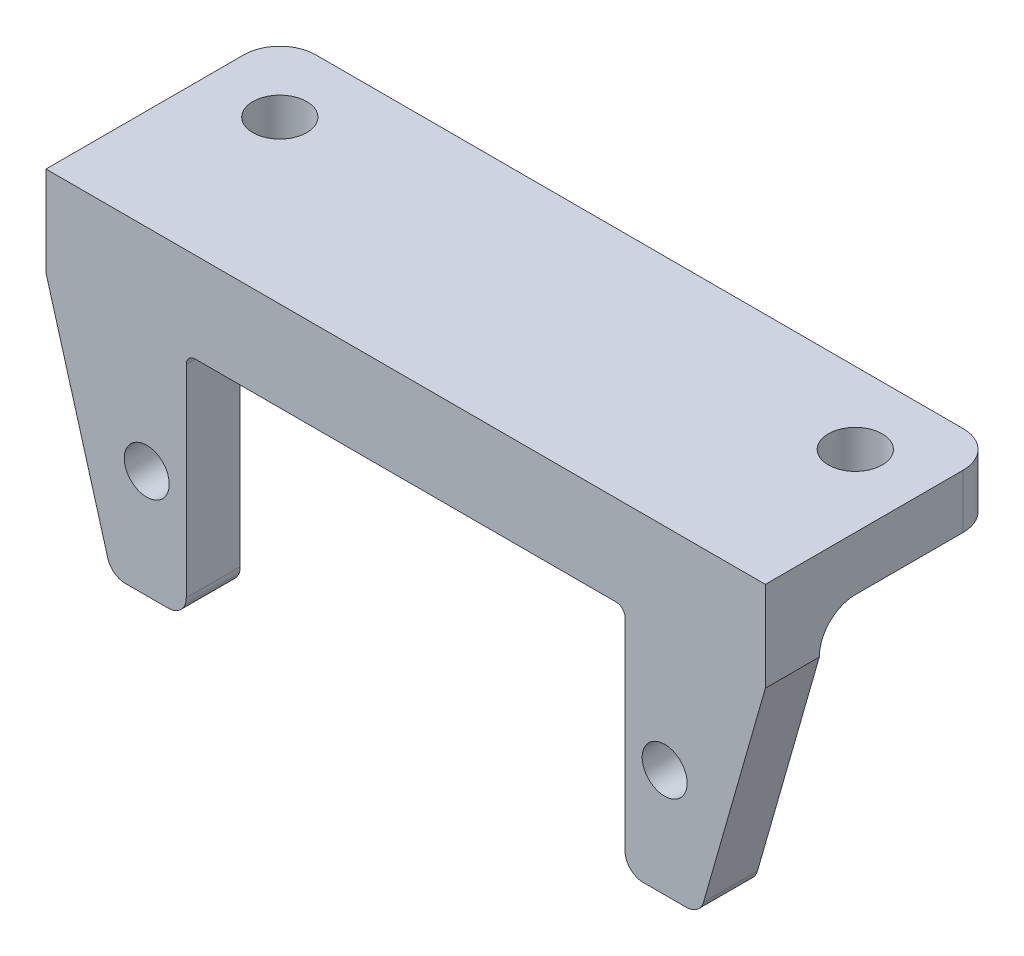
SolidWorks part; units mm, degrees
ref_plane "Front Plane" through (0, 0, 0) normal (0, 0, 1) x (1, 0, 0)
ref_plane "Top Plane" through (0, 0, 0) normal (0, 1, 0) x (1, 0, 0)
ref_plane "Right Plane" through (0, 0, 0) normal (1, 0, 0) x (0, 0, -1)
sketch "Sketch1" plane through (0, 0, 0) normal (0, 0, 1) x (1, 0, 0)
  line L1 (-15.9, -6.25) -> (15.9, -6.25)
  line L2 (-15.9, -6.25) -> (-15.9, 6.25)
  line L3 (-15.9, 6.25) -> (15.9, 6.25)
  line L4 (15.9, -6.25) -> (15.9, 6.25)
  line L5 (-15.9, -6.25) -> (15.9, 6.25) construction
  line L6 (-15.9, 6.25) -> (15.9, -6.25) construction
  line L7 (11.7, -6.25) -> (-11.7, -6.25)
  line L8 (11.7, -6.25) -> (11.7, 6.25)
  line L9 (11.7, 6.25) -> (-11.7, 6.25)
  line L10 (-11.7, -6.25) -> (-11.7, 6.25)
  line L11 (11.7, -6.25) -> (-11.7, 6.25) construction
  line L12 (11.7, 6.25) -> (-11.7, -6.25) construction
  circle A0 centre (-14.4, 0) radius 1
  circle A1 centre (-14.4, 3.5) radius 1
  circle A2 centre (-14.4, -3.5) radius 1
  circle A3 centre (14.4, 0) radius 1
  circle A4 centre (14.4, 3.5) radius 1
  circle A5 centre (14.4, -3.5) radius 1
  point P0 (0, 0)
  point P20 (0, 0)
  dimension "D3" = 2
  dimension "D1" = 31.8
  dimension "D2" = 12.5
  dimension "D4" = 1.5
  dimension "D5" = 3.5
  dimension "D6" = 3.5
  dimension "D7" = 1.5
  dimension "D8" = 23.4
sketch "Sketch3" plane through (0, 0, 0) normal (0, 0, 1) x (1, 0, 0)
  line L0 (-12.2, 6.25) -> (-12.2, -5)
  line L1 (-11.7, -6.25) -> (-11.7, 6.25) construction
  line L2 (-13.2, -6) -> (-15.6, -6)
  line L3 (-16.5615, -5.2749) -> (-20, 6.75)
  line L4 (12.2, 6.25) -> (12.2, -5)
  line L5 (11.7, -6.25) -> (11.7, 6.25) construction
  line L6 (13.2, -6) -> (15.6, -6)
  line L7 (16.5615, -5.2749) -> (20, 6.75)
  line L8 (-11.7, 6.75) -> (11.7, 6.75)
  line L9 (-15.9, 6.25) -> (15.9, 6.25) construction
  line L12 (-20, 11.75) -> (20, 11.75)
  line L15 (-20, 6.75) -> (-20, 11.75)
  line L17 (20, 6.75) -> (20, 11.75)
  circle A0 centre (-14.4, 0) radius 1.25
  circle A1 centre (14.4, 0) radius 1.25
  arc A2 (-12.2, -5) -> (-13.2, -6) centre (-13.2, -5) cw
  arc A3 (-15.6, -6) -> (-16.5615, -5.2749) centre (-15.6, -5) cw
  arc A4 (13.2, -6) -> (12.2, -5) centre (13.2, -5) cw
  arc A5 (16.5615, -5.2749) -> (15.6, -6) centre (15.6, -5) cw
  arc A6 (-11.7, 6.75) -> (-12.2, 6.25) centre (-11.7, 6.25) ccw
  arc A7 (12.2, 6.25) -> (11.7, 6.75) centre (11.7, 6.25) ccw
  point P12 (0, 0)
  point P16 (14.4, -6)
  point P22 (-12.2, -6)
  point P25 (-16.3541, -6)
  point P27 (-14.4, -6)
  point P30 (12.2, -6)
  point P31 (0, 0)
  point P39 (0, 0)
  point P40 (0, 0)
  point P42 (0, 0)
  point P43 (-19.7867, 6.75)
  point P44 (-19.5, 5.6221)
  point P45 (-19.4815, 5.7604)
  point P46 (0, 0)
  point P47 (0, 0)
  point P49 (0, 0)
  point P50 (0, 0)
  point P51 (0, 0)
  point P52 (0, 11.75)
  point P53 (0, 0)
  point P54 (0, 0)
  point P55 (0, 0)
  dimension "D1" = 2.5
  dimension "D9" = 1
  dimension "D10" = 1
  dimension "D11" = 1
  dimension "D6" = 1
  dimension "D12" = 0.5
  dimension "D13" = 0.5
  dimension "D2" = 0.5
  dimension "D4" = 0.5
  dimension "D8" = 0.5
  dimension "D5" = 6
  dimension "D18" = 40
  dimension "D14" = 5
extrude "Boss-Extrude1" add sketch "Sketch3" along normal blind 3
sketch "Sketch4" plane through (0, 0, 0) normal (0, 0, -1) x (-1, 0, 0)
  line L2 (20, 11.75) -> (20, 6.75) construction
  line L3 (-20, 11.75) -> (20, 11.75)
  line L4 (-20, 11.75) -> (-20, 8.75)
  line L5 (-20, 8.75) -> (20, 8.75)
  line L6 (20, 11.75) -> (20, 8.75)
  point P9 (-20, 8.75)
  point P12 (20, 8.75)
  dimension "D1" = 3
extrude "Boss-Extrude2" add sketch "Sketch4" along normal blind 10
fillet "Fillet1" radius 2 1 edges at (0, 8.75, 0)
fillet "Fillet2" radius 2 2 edges at (-20, 10.25, -10) (20, 10.25, -10)
sketch "Sketch5" plane through (0, 8.75, 0) normal (0, -1, 0) x (1, 0, 0)
  line L0 (-20, -8) -> (-20, -2) construction
  line L2 (18, -10) -> (-18, -10) construction
  circle A0 centre (-16, -6) radius 1.5
  dimension "D1" = 3
  dimension "D2" = 4
  dimension "D3" = 4
extrude "Cut-Extrude1" cut sketch "Sketch5" against normal through all
mirror "Mirror1" about plane through (0, 0, 0) normal (1, 0, 0) of "Cut-Extrude1"
equation "\"D6@Sketch1\"=\"D5@Sketch1\""
equation "\"D7@Sketch1\"=\"D4@Sketch1\""
equation "\"D4@Sketch3\"=\"D2@Sketch3\""
equation "\"D8@Sketch3\"=\"D2@Sketch3\""
